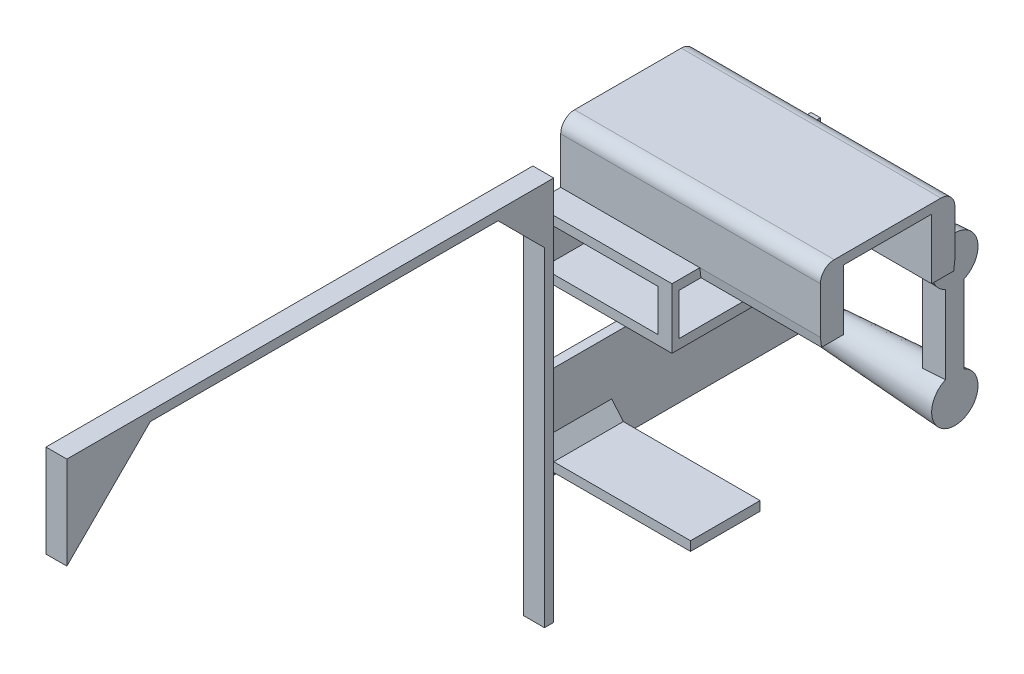
SolidWorks part; units mm, degrees
ref_plane "Front Plane" through (0, 0, 0) normal (0, 0, 1) x (1, 0, 0)
ref_plane "Top Plane" through (0, 0, 0) normal (0, 1, 0) x (1, 0, 0)
ref_plane "Right Plane" through (0, 0, 0) normal (1, 0, 0) x (0, 0, -1)
sketch "Sketch6" plane through (0, 0, 0) normal (1, 0, 0) x (0, 0, -1)
  line L1 (0, 0) -> (105, 0)
  line L2 (0, 0) -> (0, -83)
  line L3 (0, -83) -> (105, -83)
  line L4 (105, 0) -> (105, -83)
  dimension "D1" = 105
  dimension "D2" = 83
extrude "Boss-Extrude3" add sketch "Sketch6" along normal blind 4.5
sketch "Sketch9" plane through (0, -83, 0) normal (0, -1, 0) x (1, 0, 0)
  line L0 (4.5, 0) -> (4.5, -105) construction
  line L1 (0, 0) -> (0, -105) construction
  line L2 (4.5, -2) -> (1.5, -2)
  line L3 (4.5, -2) -> (4.5, -103)
  line L4 (4.5, -103) -> (1.5, -103)
  line L5 (1.5, -2) -> (1.5, -103)
  line L6 (4.5, 0) -> (0, 0) construction
  line L7 (4.5, -105) -> (0, -105) construction
  dimension "D1" = 1.5
  dimension "D2" = 2
  dimension "D3" = 2
extrude "Cut-Extrude6" cut sketch "Sketch9" against normal blind 81
sketch "Sketch10" plane through (0, 0, -2) normal (0, 0, -1) x (-1, 0, 0)
  line L1 (-4.5, -2) -> (-3.5, -2)
  line L2 (-4.5, -2) -> (-4.5, -10)
  line L3 (-4.5, -10) -> (-3.5, -10)
  line L4 (-3.5, -2) -> (-3.5, -10)
  dimension "D1" = 1
  dimension "D2" = 8
extrude "Boss-Extrude4" add sketch "Sketch10" along normal blind 8
sketch "Sketch11" plane through (0, 0, -103) normal (0, 0, 1) x (1, 0, 0)
  line L1 (4.5, -2) -> (3.5, -2)
  line L2 (4.5, -2) -> (4.5, -7)
  line L3 (4.5, -7) -> (3.5, -7)
  line L4 (3.5, -2) -> (3.5, -7)
  dimension "D1" = 5
  dimension "D2" = 1
extrude "Boss-Extrude5" add sketch "Sketch11" along normal blind 5
sketch "Sketch18" plane through (4.5, 0, 0) normal (1, 0, 0) x (0, 0, -1)
  line L0 (103, -12) -> (93, -2)
  line L1 (103, -7) -> (103, -83) construction
  line L2 (98, -2) -> (10, -2) construction
  line L3 (103, -12) -> (103, -2)
  line L4 (103, -2) -> (93, -2)
  line L5 (18, -2) -> (2, -2)
  line L6 (2, -2) -> (2, -18)
  line L7 (2, -10) -> (2, -83) construction
  line L8 (2, -18) -> (18, -2)
  dimension "D1" = 0
  dimension "D2" = 10
  dimension "D3" = 0
  dimension "D4" = 16
  dimension "D5" = 22.6274
extrude "Boss-Extrude12" add sketch "Sketch18" against normal up to vertex (1 mm away) up to point (3.5, -7, -98)
sketch "Sketch27" plane through (0, 0, 0) normal (-1, 0, 0) x (0, 0, 1)
  line L0 (-105, -83) -> (-105, 0) construction
  line L1 (-105, -55) -> (-120, -55)
  line L2 (-105, -55) -> (-105, -53)
  line L3 (-105, -53) -> (-120, -53)
  line L4 (-120, -55) -> (-120, -53)
  line L5 (-125.5, -18) -> (-125.5, 21.7068) construction
  line L6 (-105, -20) -> (-146, -20)
  line L7 (-105, -20) -> (-105, -18)
  line L8 (-105, -18) -> (-146, -18)
  line L9 (-146, -20) -> (-146, -18)
  line L10 (-105, -9) -> (-116, -9)
  line L11 (-105, -9) -> (-105, 6)
  line L12 (-105, 6) -> (-116, 6)
  line L13 (-116, -9) -> (-116, 6)
  line L14 (-146, 6) -> (-135, 6)
  line L15 (-135, -9) -> (-135, 6)
  line L16 (-146, -9) -> (-135, -9)
  line L17 (-146, -9) -> (-146, 6)
  dimension "D1" = 15
  dimension "D2" = 28
  dimension "D3" = 63
  dimension "D4" = 41
  dimension "D5" = 2
  dimension "D6" = 2
  dimension "D7" = 9
  dimension "D8" = 15
  dimension "D9" = 11
extrude "Boss-Extrude20" add sketch "Sketch27" against normal blind 30
sketch "Sketch28" plane through (30, 0, 0) normal (1, 0, 0) x (0, 0, -1)
  line L0 (146, -9) -> (135, -9) construction
  line L1 (146, -20) -> (144.5, -20)
  line L2 (146, -20) -> (146, -9)
  line L3 (146, -9) -> (144.5, -9)
  line L4 (144.5, -20) -> (144.5, -9)
  line L5 (125.5, -18) -> (125.5, -4.7212) construction
  line L6 (105, -18) -> (146, -18) construction
  line L7 (105, -9) -> (106.5, -9)
  line L8 (106.5, -20) -> (106.5, -9)
  line L9 (105, -20) -> (106.5, -20)
  line L10 (105, -20) -> (105, -9)
  dimension "D1" = 1.5
extrude "Boss-Extrude21" add sketch "Sketch28" against normal blind 3
sketch "Sketch29" plane through (30, 0, 0) normal (1, 0, 0) x (0, 0, -1)
  line L0 (105, -20) -> (105, 6) construction
  line L1 (146, 6) -> (105, 6)
  line L2 (146, 6) -> (146, 4)
  line L3 (146, 4) -> (105, 4)
  line L4 (105, 6) -> (105, 4)
  dimension "D1" = 2
extrude "Boss-Extrude22" add sketch "Sketch29" against normal up to vertex (30 mm away) up to point (0, 6, -105)
sketch "Sketch30" plane through (0, 0, -105) normal (0, 0, -1) x (-1, 0, 0)
  line L0 (0, -83) -> (0, -55) construction
  line L1 (0, -58) -> (-2, -58)
  line L2 (0, -58) -> (0, -20)
  line L3 (0, -20) -> (-2, -20)
  line L4 (-2, -58) -> (-2, -20)
  dimension "D1" = 2
  dimension "D2" = 25
  dimension "D3" = 0
extrude "Boss-Extrude23" add sketch "Sketch30" along normal blind 60
sketch "Sketch31" plane through (2, 0, 0) normal (1, 0, 0) x (0, 0, -1)
  line L0 (165, -58) -> (105, -58) construction
  line L1 (165, -20) -> (165, -58) construction
  line L2 (165, -39) -> (129.1416, -39) construction
  circle A0 centre (159, -52) radius 5
  circle A1 centre (159, -26) radius 5
  dimension "D1" = 10
  dimension "D2" = 6
  dimension "D3" = 6
extrude "Boss-Extrude24" add sketch "Sketch31" along normal blind 35
draft "Draft1" type of draft neutral plane draft angle 3.5 faces to draft 1 face at (37, -52, -164) neutral plane through (37, -52, -159) neutral plane normal (1, 0, 0) reverse direction yes parameters "D1"=3.5
draft "Draft3" type of draft neutral plane draft angle 3.5 faces to draft 1 face at (37, -26, -154) neutral plane through (37, -26, -159) neutral plane normal (1, 0, 0) reverse direction yes parameters "D1"=3.5
sketch "Sketch32" plane through (2, 0, 0) normal (1, 0, 0) x (0, 0, -1)
  line L1 (161, -53) -> (157, -53)
  line L2 (161, -53) -> (161, -25)
  line L3 (161, -25) -> (157, -25)
  line L4 (157, -53) -> (157, -25)
  circle A0 centre (159, -52) radius 2.8593 construction
  circle A1 centre (159, -26) radius 2.8593 construction
  dimension "D1" = 2
  dimension "D2" = 2
  dimension "D3" = 1
  dimension "D4" = 1
  dimension "D5" = 2
extrude "Boss-Extrude25" add sketch "Sketch32" along normal blind 7
sketch "Sketch33" plane through (37, 0, 0) normal (1, 0, 0) x (0, 0, -1)
  line L1 (157, -26) -> (161, -26)
  line L2 (157, -26) -> (157, -52)
  line L3 (157, -52) -> (161, -52)
  line L4 (161, -26) -> (161, -52)
  circle A0 centre (159, -26) radius 5 construction
  circle A1 centre (159, -52) radius 5 construction
  point P6 (159, -26)
  dimension "D1" = 0
  dimension "D2" = 4
  dimension "D3" = 0
  dimension "D4" = 0
extrude "Boss-Extrude26" add sketch "Sketch33" against normal blind 5
sketch "Sketch39" plane through (0, 0, 0) normal (-1, 0, 0) x (0, 0, 1)
  line L0 (-105, -18) -> (-105, -9) construction
  line L1 (-146, 6) -> (-105, 6)
  line L2 (-146, 6) -> (-146, -18)
  line L3 (-146, -18) -> (-105, -18)
  line L4 (-105, 6) -> (-105, -18)
  line L5 (-105, -18) -> (-146, -18) construction
  dimension "D1" = 0
  dimension "D2" = 0
extrude "Boss-Extrude30" add sketch "Sketch39" against normal blind 2
sketch "Sketch40" plane through (2, 0, 0) normal (1, 0, 0) x (0, 0, -1)
  line L1 (116, 4) -> (135, 4) construction
  line L2 (116, -9) -> (116, 4) construction
  circle A0 centre (125.5, -6.5) radius 5
  point P4 (125.5, 4)
  point P7 (116, -2.5)
  dimension "D1" = 0
  dimension "D2" = 4
  dimension "D3" = 10
extrude "Cut-Extrude9" cut sketch "Sketch40" against normal blind 2
sketch "Sketch41" plane through (0, 0, -120) normal (0, 0, -1) x (-1, 0, 0)
  line L0 (-2, -54) -> (-7.9406, -54) construction
  line L1 (-2, -55) -> (-2, -53) construction
  line L2 (-2, -55) -> (-2, -58)
  line L3 (-2, -58) -> (-4.5, -55)
  line L4 (-30, -55) -> (-2, -55) construction
  line L5 (-4.5, -55) -> (-2, -55)
  line L7 (-2, -50) -> (-4.5, -53)
  line L8 (-2, -53) -> (-2, -50)
  line L9 (-4.5, -53) -> (-2, -53)
  dimension "D1" = 0
  dimension "D2" = 0
extrude "Boss-Extrude31" add sketch "Sketch41" along direction (0, 0, 1) on the side against the normal up to surface (15 mm away) up to face at (2.1667, -65.3333, -105)
sketch "Sketch42" plane through (30, 0, 0) normal (1, 0, 0) x (0, 0, -1)
  line L1 (105, -55) -> (120, -55)
  line L2 (105, -55) -> (105, -53)
  line L3 (105, -53) -> (120, -53)
  line L4 (120, -55) -> (120, -53)
extrude "Boss-Extrude32" add sketch "Sketch42" along normal blind 4
sketch "Sketch45" plane through (2, 0, 0) normal (1, 0, 0) x (0, 0, -1)
  line L0 (165, -58) -> (120, -58) construction
  line L1 (105, -20) -> (135, -20)
  line L2 (105, -20) -> (105, -38)
  line L3 (105, -38) -> (135, -38)
  line L4 (135, -20) -> (135, -38)
  line L5 (165, -20) -> (165, -58) construction
  dimension "D1" = 20
  dimension "D2" = 30
extrude "Cut-Extrude10" cut sketch "Sketch45" against normal blind 5
fillet "Fillet1" radius 4 1 edges at (15, 6, -146)
fillet "Fillet2" radius 4 1 edges at (15, 6, -105)
sketch "Sketch46" plane through (4.5, 0, 0) normal (1, 0, 0) x (0, 0, -1)
  line L0 (18, -2) -> (0, -20)
  line L1 (0, 0) -> (0, -83) construction
  line L2 (0, -20) -> (0, -83)
  line L3 (0, -83) -> (103, -83)
  line L4 (103, -83) -> (103, -12)
  line L5 (103, -12) -> (93, -2)
  line L6 (93, -2) -> (18, -2)
extrude "Cut-Extrude11" cut sketch "Sketch46" against normal blind 10
sketch "Sketch47" plane through (1.5, 0, 0) normal (1, 0, 0) x (0, 0, -1)
  line L0 (93, -2) -> (103, -2)
  line L1 (103, -2) -> (103, -12)
  line L2 (103, -12) -> (93, -2)
  line L3 (2, -18) -> (18, -2)
  line L4 (18, -2) -> (2, -2)
  line L5 (2, -2) -> (18, -2) construction
  line L6 (2, -2) -> (2, -18) construction
  line L7 (2, -2) -> (2, -18)
extrude "Cut-Extrude12" cut sketch "Sketch47" against normal blind 0.5
sketch "Sketch48" plane through (2, 0, 0) normal (1, 0, 0) x (0, 0, -1)
  line L0 (116, 4) -> (116, -9)
  line L1 (116, -9) -> (135, -9)
  line L2 (135, -9) -> (135, 4)
  line L3 (135, 4) -> (116, 4)
extrude "Boss-Extrude33" add sketch "Sketch48" along normal blind 10
sketch "Sketch49" plane through (30, 0, 0) normal (1, 0, 0) x (0, 0, -1)
  line L0 (105, -7) -> (111, -7)
  line L1 (105, -20) -> (105, 2) construction
  line L2 (111, -7) -> (111, 6)
  line L3 (109, 6) -> (142, 6) construction
  line L4 (111, 6) -> (105, 6)
  line L5 (105, 6) -> (105, -7)
  line L6 (125.5, 6) -> (125.5, -8.6128) construction
  line L7 (116, 4) -> (116, -9) construction
  line L8 (116, -9) -> (106.5, -9) construction
  line L9 (140, 6) -> (146, 6)
  line L10 (140, -7) -> (140, 6)
  line L11 (146, -7) -> (140, -7)
  line L12 (146, 6) -> (146, -7)
  dimension "D1" = 5
  dimension "D2" = 2
extrude "Cut-Extrude13" cut sketch "Sketch49" against normal up to vertex (30 mm away) up to point (0, 0, -105)
sketch "Sketch50" plane through (30, 0, 0) normal (1, 0, 0) x (0, 0, -1)
  line L1 (116, -9) -> (106.5, -9) construction
  line L2 (111.25, -9) -> (116, -9)
  line L3 (116, -9) -> (116, 4)
  line L4 (116, 4) -> (135, 4)
  line L5 (135, 4) -> (135, -9)
  line L6 (135, -9) -> (139.75, -9)
  line L7 (144.5, -9) -> (135, -9) construction
  line L9 (140, 6) -> (111, 6)
  line L10 (140, 6) -> (140, -7)
  line L11 (140, 6) -> (140, -7) construction
  line L12 (140, -7) -> (139.75, -9)
  line L13 (111, 6) -> (111, -7)
  line L14 (111, -7) -> (111.25, -9)
extrude "Boss-Extrude34" add sketch "Sketch50" along normal blind 26
fillet "Fillet3" radius 3 1 edges at (28, 6, -140)
fillet "Fillet4" radius 3 1 edges at (28, 6, -111)
